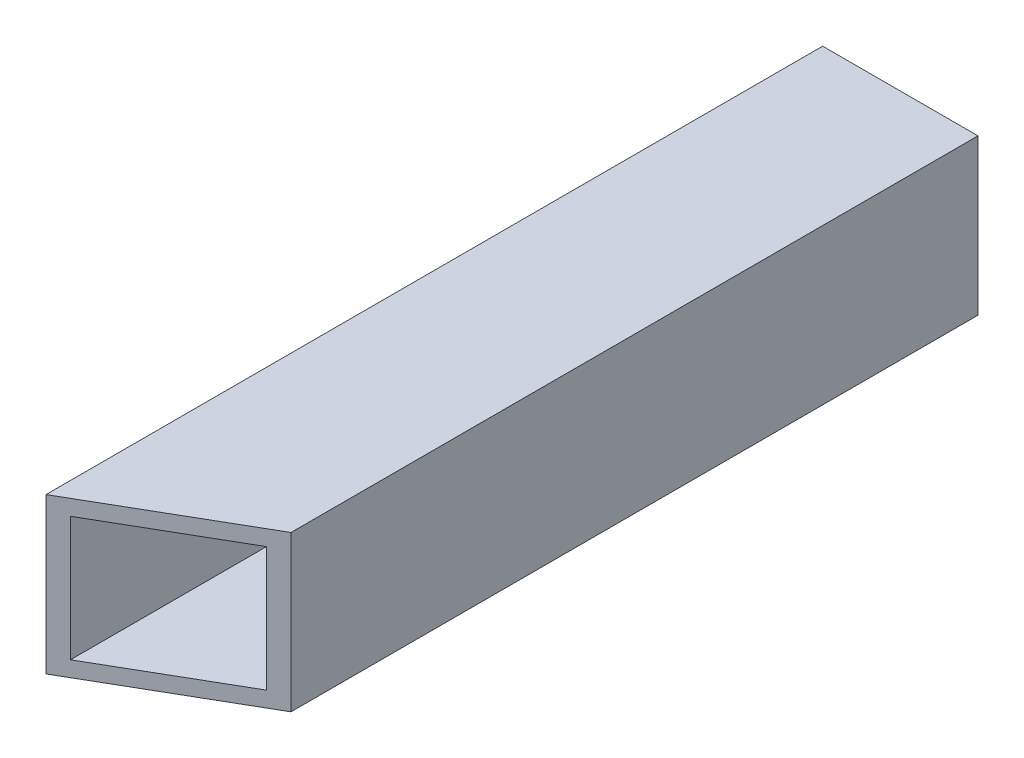
SolidWorks part; units mm, degrees
ref_plane "Front Plane" through (0, 0, 0) normal (0, 0, 1) x (1, 0, 0)
ref_plane "Top Plane" through (0, 0, 0) normal (0, 1, 0) x (1, 0, 0)
ref_plane "Right Plane" through (0, 0, 0) normal (1, 0, 0) x (0, 0, -1)
sketch "Sketch2" plane through (0, 0, 0) normal (0, 0, 1) x (1, 0, 0)
  line L0 (-10.16, 10.16) -> (10.16, 10.16)
  line L1 (-12.7, -12.7) -> (12.7, -12.7)
  line L2 (-12.7, -12.7) -> (-12.7, 12.7)
  line L3 (-12.7, 12.7) -> (12.7, 12.7)
  line L4 (12.7, -12.7) -> (12.7, 12.7)
  line L5 (-12.7, -12.7) -> (12.7, 12.7) construction
  line L6 (-12.7, 12.7) -> (12.7, -12.7) construction
  line L7 (10.16, -10.16) -> (10.16, 10.16)
  line L8 (-10.16, -10.16) -> (10.16, -10.16)
  line L9 (-10.16, -10.16) -> (-10.16, 10.16)
  point P0 (0, 0)
  dimension "D1" = 25.4
  dimension "D2" = 25.4
  dimension "D3" = 2.54
extrude "Boss-Extrude1" add sketch "Sketch2" along normal blind 127
sketch "Sketch3" plane through (0, -12.7, 0) normal (0, -1, 0) x (-1, 0, 0)
  line L0 (12.7, -127) -> (-12.7, -112.3353)
  line L1 (-12.7, -127) -> (-12.7, 0) construction
  line L2 (-12.7, -112.3353) -> (-12.7, -127)
  line L3 (-12.7, -127) -> (12.7, -127)
  dimension "D1" = 30
extrude "Cut-Extrude1" cut sketch "Sketch3" against normal through all
